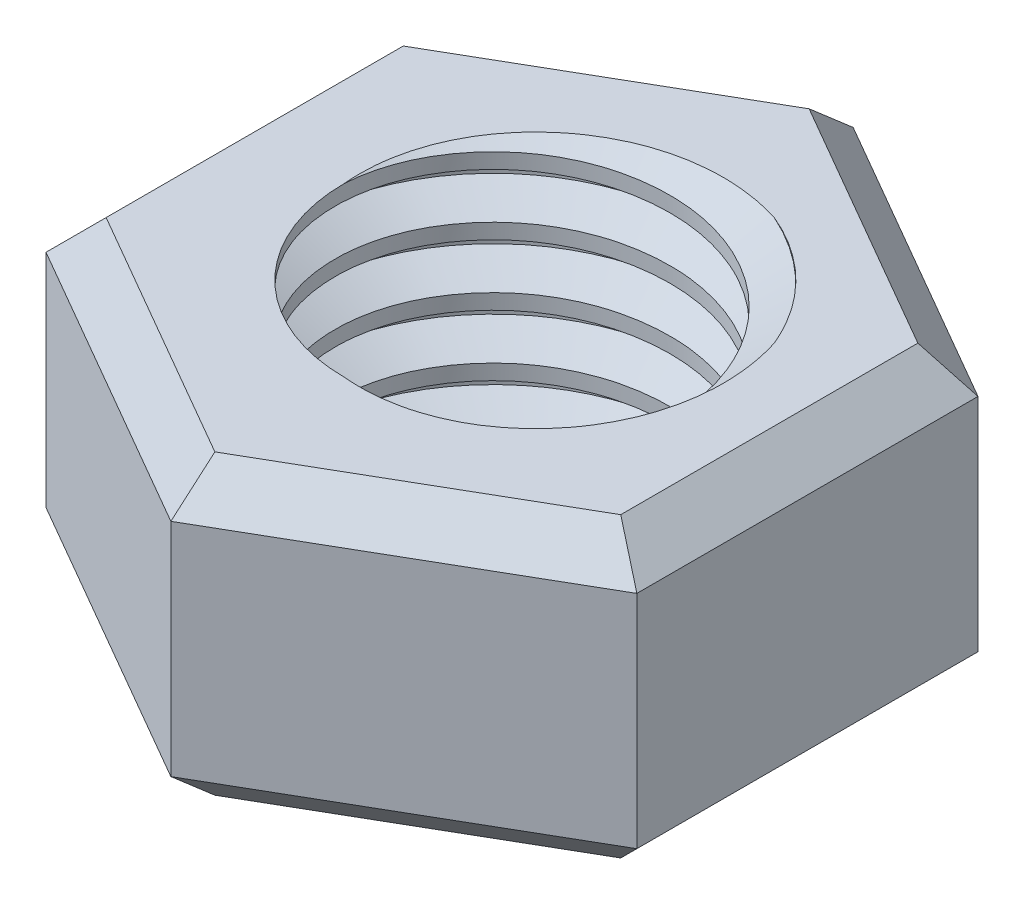
SolidWorks part; units mm, degrees
ref_plane "Front Plane" through (0, 0, 0) normal (0, 0, 1) x (1, 0, 0)
ref_plane "Top Plane" through (0, 0, 0) normal (0, 1, 0) x (1, 0, 0)
ref_plane "Right Plane" through (0, 0, 0) normal (1, 0, 0) x (0, 0, -1)
sketch "Sketch1" plane through (0, 0, 0) normal (0, 1, 0) x (1, 0, 0)
  line L1 (0, -4.4745) -> (3.875, -2.2372)
  line L2 (3.875, -2.2372) -> (3.875, 2.2372)
  line L3 (3.875, 2.2372) -> (0, 4.4745)
  line L4 (0, 4.4745) -> (-3.875, 2.2372)
  line L5 (-3.875, 2.2372) -> (-3.875, -2.2372)
  line L6 (-3.875, -2.2372) -> (0, -4.4745)
  circle A0 centre (0, 0) radius 3.875 construction
  circle A1 centre (0, 0) radius 2.2
  dimension "D2" = 4.4
  dimension "D1" = 7.75
extrude "Boss-Extrude1" add sketch "Sketch1" along normal blind 3.9
thread "Thread1" pitch 0.8 method cut profile "Thread Profile1" start angle 0, offset 0.6, length 0, pitch 0.8, diameter 4.4
ref_plane "Plane1" through (-2.2, 4.5, 0) normal (0, 0, 1) x (-1, 0, 0)
sketch "Thread Profile1" plane through (-2.2, 4.5, 0) normal (0, 0, 1) x (-1, 0, 0)
  line L0 (0, 0) -> (0, 0.8) construction
  line L1 (0, 0) -> (0.433, 0.25)
  line L2 (0.433, 0.25) -> (0.433, 0.35)
  line L3 (0.433, 0.35) -> (0, 0.6)
  line L4 (0.433, 0.3) -> (0, 0.3) construction
  line L11 (0, 0) -> (0, 0.6)
  point P2 (0, 0)
  dimension "Pitch" = 0.8
  dimension "Profile_Angle" = 60
  dimension "Profile_Land" = 0.1
  dimension "Profile_Height" = 0.433
chamfer "Chamfer1" distance 0.5 angle 45 12 edges at (3.875, 0, 0) (1.9375, 0, 3.3558) (-1.9375, 0, 3.3558) (-3.875, 0, 0) (-1.9375, 0, -3.3558) (1.9375, 0, -3.3558) (1.9375, 3.9, -3.3558) (-1.9375, 3.9, -3.3558) (-3.875, 3.9, 0) (-1.9375, 3.9, 3.3558) (1.9375, 3.9, 3.3558) (3.875, 3.9, 0)
ref_axis "Centerline" through (0, 4.3992, 0) along (0, -1, 0)
